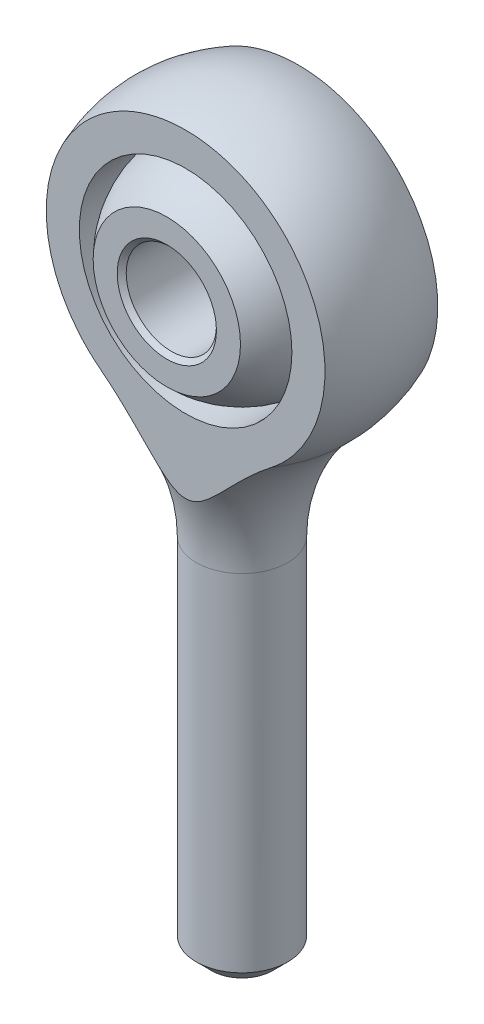
SolidWorks part; units mm, degrees
material "Cast Carbon Steel"
ref_plane "Front" through (0, 0, 0) normal (0, 0, 1) x (1, 0, 0)
ref_plane "Top" through (0, 0, 0) normal (0, 1, 0) x (1, 0, 0)
ref_plane "Right" through (0, 0, 0) normal (1, 0, 0) x (0, 0, -1)
sketch "Sketch1" plane through (0, 0, 0) normal (0, 0, 1) x (1, 0, 0)
  line L0 (0, 0) -> (0, -19.05)
  line L1 (0, -19.05) -> (2.413, -19.05)
  line L2 (2.413, -19.05) -> (2.413, 0)
  line L3 (2.413, 0) -> (0, 0)
  line L5 (0, 20.6375) -> (0, 0) construction
  line L6 (0, 20.6375) -> (7.9375, 20.6375) construction
  line L7 (7.9375, 20.6375) -> (7.9375, 12.7) construction
  line L8 (-2.413, -19.05) -> (-2.413, 0) construction
  arc A0 (5.4115, 6.8932) -> (0, 20.6375) centre (0, 12.7) ccw construction
  circle A1 centre (0, 12.7) radius 2.3813 construction
  circle A2 centre (0, 12.7) radius 5.5562 construction
  circle A3 centre (0, 12.7) radius 5.6118 construction
  arc A4 (2.413, 0) -> (5.4115, 6.8932) centre (11.8355, 0) cw construction
  dimension "A" = 4.7625
  dimension "Ball Dia" = 11.1125
  dimension "B" = 15.875
  dimension "D1" = 11.2236
  dimension "D" = 31.75
  dimension "E" = 19.05
  dimension "Thread Dia" = 4.826
revolve "Revolve1" add sketch "Sketch1" angle 360 about L5
chamfer "Chamfer2" distance 0.795 angle 45 1 edges at (-2.413, -19.05, 0)
sketch "Sketch12" plane through (0, -19.05, 0) normal (0, -1, 0) x (1, 0, 0)
  circle A1 centre (0, 0) radius 1.618
  circle A2 centre (0, 0) radius 1.618
  dimension "D1" = 0
curve "Helix/Spiral1" [suppressed] pitch 0.795 height 24.13 turns 30.3514
sketch "Sketch13" plane through (0, 0, 0) normal (0, 0, 1) x (1, 0, 0)
  line L0 (2.413, -19.05) -> (2.413, -19.7456)
  line L1 (2.413, -19.7456) -> (1.8966, -19.4475)
  line L2 (1.8966, -19.4475) -> (1.8966, -19.3481)
  line L3 (1.8966, -19.3481) -> (2.413, -19.05)
  line L4 (2.1548, -19.1991) -> (2.1548, -19.5966) construction
  dimension "D1" = 60
  dimension "D2" = 0.0994
  dimension "D3" = 0.3975
sweep "Cut-Sweep2" [suppressed] cut profiles "Sketch13" path "Helix/Spiral1"
sketch "Sketch4" plane through (0, 0, 0) normal (0, 0, 1) x (1, 0, 0)
  line L0 (2.413, 0) -> (0, 0) construction
  line L2 (0, 20.6375) -> (0, 0) construction
  line L3 (2.413, 0) -> (0, 0)
  line L5 (0, 20.6375) -> (0, 0)
  line L6 (0, 20.6375) -> (0, 23.1775) construction
  arc A0 (5.4115, 6.8932) -> (0, 20.6375) centre (0, 12.7) ccw construction
  arc A1 (5.4115, 6.8932) -> (0, 20.6375) centre (0, 12.7) ccw
  arc A2 (5.4115, 6.8932) -> (2.413, 0) centre (11.8355, 0) ccw construction
  arc A3 (5.4115, 6.8932) -> (2.413, 0) centre (11.8355, 0) ccw
  dimension "D1" = 2.54
revolve "Revolve2" add sketch "Sketch4" angle 360 about L6
sketch "Sketch5" plane through (0, 0, 0) normal (1, 0, 0) x (0, 0, -1)
  line L0 (2.9766, 20.6375) -> (7.9375, 20.6375)
  line L1 (-2.9766, 20.6375) -> (2.9766, 20.6375) construction
  line L2 (-2.9766, 20.6375) -> (-2.9766, 1.1906)
  line L3 (-2.413, 0) -> (2.413, 0) construction
  line L4 (2.9766, 20.6375) -> (2.9766, 1.1906)
  line L5 (7.9375, 20.6375) -> (7.9375, 0)
  line L6 (7.9375, 0) -> (2.413, 0)
  line L7 (-2.413, 0) -> (-7.9375, 0)
  line L8 (-7.9375, 0) -> (-7.9375, 20.6375)
  line L9 (-7.9375, 20.6375) -> (-2.9766, 20.6375)
  line L10 (2.413, 0) -> (2.9766, 1.1906)
  line L11 (-2.413, 0) -> (-2.9766, 1.1906)
  line L12 (-2.9766, 1.1906) -> (2.9766, 1.1906) construction
  line L13 (0, 0) -> (0, 1.1906) construction
  arc A0 (5.4115, 6.8932) -> (-5.4115, 6.8932) centre (0, 12.7) ccw construction
  dimension "F" = 5.9531
  dimension "D2" = 1.1906
  dimension "D1" = 4.826
extrude "Cut-Extrude1" cut sketch "Sketch5" against normal through all and the other way through all
sketch "Sketch6" plane through (0, 0, 0) normal (0, 0, 1) x (1, 0, 0)
  circle A0 centre (0, 12.7) radius 5.6118 construction
  circle A1 centre (0, 12.7) radius 5.6118
extrude "Cut-Extrude2" cut sketch "Sketch6" against normal through all and the other way through all
sketch "Sketch7" plane through (0, 0, 0) normal (0, 0, 1) x (1, 0, 0)
  line L0 (0, 18.2563) -> (0, 7.1438)
  line L1 (0, 20.6375) -> (0, 0) construction
  line L2 (0, 0) -> (0, 7.1438) construction
  arc A0 (0, 7.1438) -> (0, 18.2563) centre (0, 12.7) ccw
  circle A1 centre (0, 12.7) radius 5.5562 construction
revolve "Revolve3" add sketch "Sketch7" angle 360 about L2
sketch "Sketch8" plane through (0, 0, 0) normal (1, 0, 0) x (0, 0, -1)
  line L0 (-2.9766, 20.6375) -> (2.9766, 20.6375) construction
  line L1 (-3.9687, 20.6375) -> (3.9687, 20.6375) construction
  line L2 (-3.9687, 20.6375) -> (-3.9688, 0)
  line L3 (-3.9688, 0) -> (3.9688, 0) construction
  line L4 (3.9687, 20.6375) -> (3.9688, 0)
  line L5 (3.9687, 20.6375) -> (7.9375, 20.6375)
  line L6 (7.9375, 20.6375) -> (7.9375, 0)
  line L7 (7.9375, 0) -> (3.9688, 0)
  line L8 (-3.9688, 0) -> (-7.9375, 0)
  line L9 (-7.9375, 0) -> (-7.9375, 20.6375)
  line L10 (-7.9375, 20.6375) -> (-3.9687, 20.6375)
  dimension "C" = 7.9375
extrude "Cut-Extrude3" cut sketch "Sketch8" against normal through all and the other way through all
sketch "Sketch10" plane through (0, 0, 0) normal (0, 0, 1) x (1, 0, 0)
  circle A0 centre (0, 12.7) radius 2.3812 construction
  circle A1 centre (0, 12.7) radius 2.3812
extrude "Cut-Extrude4" cut sketch "Sketch10" against normal through all and the other way through all
chamfer "Chamfer1" distance 0.2381 angle 45 2 edges at (2.3812, 12.7, -3.9688) (2.3812, 12.7, 3.9687)
sketch "Sketch14" [suppressed] plane through (0, 0, 0) normal (1, 0, 0) x (0, 0, -1)
  line L0 (2.4016, 13.0969) -> (-2.4016, 13.0969) construction
  line L1 (3.9688, 13.0969) -> (-3.9688, 13.0969)
  line L2 (-3.9688, 13.0969) -> (-3.9688, 13.6049)
  line L3 (-2.6, 13.5616) -> (2.6, 13.5616)
  line L4 (-2.6, 13.5616) -> (-2.6, 8.6634) construction
  line L5 (3.9688, 13.6049) -> (3.9688, 13.0969)
  arc A0 (-3.9688, 13.6049) -> (-2.6, 13.5616) centre (-3.9688, -8.0834) cw
  arc A1 (2.6, 13.5616) -> (3.9688, 13.6049) centre (3.9688, -8.0834) cw
  point P11 (0, 13.0969)
  dimension "D1" = 7.9375
  dimension "D2" = 0.508
revolve "Revolve4" [suppressed] add sketch "Sketch14" angle 360
fillet "Fillet1" [suppressed] radius 0.508
sketch "Sketch11" plane through (0, 0, 0) normal (1, 0, 0) x (0, 0, -1)
  line L0 (0, 12.7) -> (-3.9687, 13.3998) construction
  line L1 (2.9766, 12.7) -> (-2.9766, 12.7) construction
  line L2 (0, 12.7) -> (-3.9687, 12.0002) construction
  line L3 (0, 20.6375) -> (0, 0) construction
  line L4 (-3.9687, 20.6375) -> (-3.9688, 0) construction
  line L5 (0, 12.7) -> (0.0074, 12.7) construction
  dimension "Swivel" = 20
sketch "Sketch15" plane through (0, 0, 0) normal (1, 0, 0) x (0, 0, -1)
  line L0 (-3.7306, 10.3188) -> (3.7306, 10.3188) construction
  line L1 (3.7306, 15.0813) -> (-3.7306, 15.0813) construction
  line L2 (-3.7306, 10.3188) -> (3.7306, 10.3188) construction
  line L3 (3.7306, 15.0813) -> (-3.7306, 15.0813) construction
  line L4 (-2.9766, 20.0583) -> (-2.9766, 6.8932) construction
  line L5 (2.9766, 6.8932) -> (2.9766, 20.0583) construction
  arc A0 (-3.9688, 8.8114) -> (3.9688, 8.8114) centre (0, 12.7) ccw construction
  arc A1 (3.9688, 16.5886) -> (-3.9688, 16.5886) centre (0, 12.7) ccw construction
  arc A2 (-2.9766, 8.0083) -> (2.9766, 8.0083) centre (0, 12.7) ccw construction
  arc A3 (2.9766, 17.3917) -> (-2.9766, 17.3917) centre (0, 12.7) ccw construction
equation "\"D1@Sketch1\"=\"Ball Dia@Sketch1\"*1.01"
equation "\"D1@Chamfer1\"=\"A@Sketch1\"/20"
equation "\"D1@Sketch5\"=\"Thread Dia@Sketch1\""
equation "\"D2@Sketch5\"=\"F@Sketch5\"/5"
equation "\"D3@Helix/Spiral1\" = \"E@Sketch1\" + .2"
equation "\"D2@Sketch13\" = \"D4@Helix/Spiral1\" * .125"
equation "\"D3@Sketch13\" = \"D4@Helix/Spiral1\" * .5"
equation "\"D1@Chamfer2\" = \"D4@Helix/Spiral1\" * 1"
